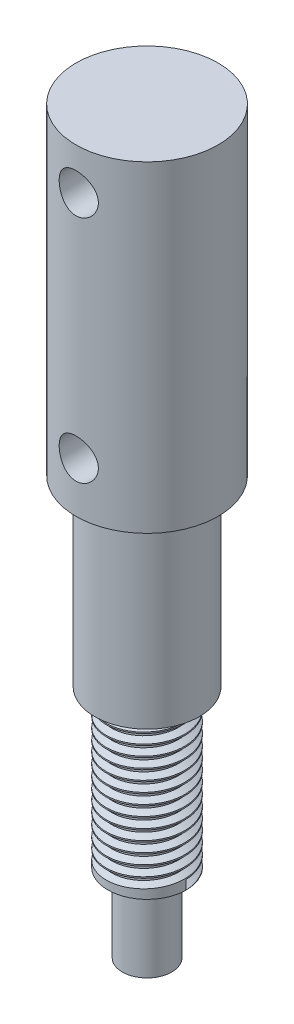
SolidWorks part; units mm, degrees
material "AISI 316 Annealed Stainless Steel Bar (SS)"
ref_plane "Front Plane" through (0, 0, 0) normal (0, 0, 1) x (1, 0, 0)
ref_plane "Top Plane" through (0, 0, 0) normal (0, 1, 0) x (1, 0, 0)
ref_plane "Right Plane" through (0, 0, 0) normal (1, 0, 0) x (0, 0, -1)
sketch "Sketch2" plane through (0, 0, 0) normal (0, 0, 1) x (1, 0, 0)
  line L0 (0, 0) -> (0, 508.8276) construction
  line L1 (0, 0) -> (6, 0)
  line L2 (0, 0) -> (0, 19.05)
  line L3 (0, 19.05) -> (6, 19.05)
  line L4 (6, 0) -> (6, 19.05)
  line L5 (0, 19.05) -> (9.525, 19.05)
  line L6 (0, 19.05) -> (0, 57.15)
  line L7 (0, 57.15) -> (9.525, 57.15)
  line L8 (9.525, 19.05) -> (9.525, 57.15)
  line L9 (0, 57.15) -> (12.721, 57.15)
  line L10 (0, 57.15) -> (0, 101.6)
  line L11 (0, 101.6) -> (12.721, 101.6)
  line L12 (12.721, 57.15) -> (12.721, 101.6)
  line L13 (0, 101.6) -> (17.272, 101.6)
  line L14 (0, 101.6) -> (0, 179.832)
  line L15 (0, 179.832) -> (17.272, 179.832)
  line L16 (17.272, 101.6) -> (17.272, 179.832)
  dimension "D1" = 78.232
  dimension "D2" = 17.272
  dimension "D4" = 44.45
  dimension "D3" = 12.721
  dimension "D5" = 38.1
  dimension "D6" = 9.525
  dimension "D7" = 19.05
  dimension "D8" = 6
revolve "Revolve1" add sketch "Sketch2" angle 360 about L0 region at (3, 9.525, 0) region at (4.7625, 38.1, 0) region at (6.3605, 79.375, 0) region at (8.636, 140.716, 0)
thread "Thread2" pitch 2.54 method cut profile "Thread Profile3" start angle 0, offset 0, length 0, pitch 2.54, diameter 19.05
ref_plane "Plane3" through (9.525, 19.05, 0) normal (0, 0, 1) x (1, 0, 0)
sketch "Thread Profile3" plane through (9.525, 19.05, 0) normal (0, 0, 1) x (1, 0, 0)
  line L0 (0, 0) -> (0, 2.54) construction
  line L11 (0, 0) -> (0, 2.2225)
  line L12 (0, 2.2225) -> (-1.3748, 1.4287)
  line L13 (-1.3748, 1.4287) -> (-1.3748, 0.7937)
  line L15 (-1.3748, 0.7937) -> (0, 0)
  line L17 (-1.3748, 1.1112) -> (0, 1.1112) construction
  point P2 (0, 0)
  dimension "Pitch" = 2.54
  dimension "Profile_Angle" = 60
  dimension "Profile_Land" = 0.635
  dimension "Profile_Height" = 1.3748
sketch "Sketch3" plane through (0, 0, 0) normal (0, 0, 1) x (1, 0, 0)
  line L0 (0, 0) -> (0, 197.3408) construction
  line L1 (17.272, 179.832) -> (-17.272, 179.832) construction
  circle A0 centre (0, 169.672) radius 4.7625
  circle A1 centre (0, 113.792) radius 4.7625
  dimension "D1" = 9.525
  dimension "D2" = 10.16
  dimension "D3" = 66.04
extrude "Cut-Extrude1" cut sketch "Sketch3" against normal through all both and the other way through all
equation "\"hole diamiter\"= 1.36in"
equation "\"wheel depth\"= 2.88"
equation "\"press_tolerance\"= 0.00165"
equation "\"wheel_connection\"= \"hole diamiter\"'https://at-machining.com/tolerance-press-fit/"
equation "\"D1@Sketch2\"=\"wheel depth\"+0.2"
equation "\"D2@Sketch2\"=\"wheel_connection\"/2"
equation "\"fitting depth\"=1.75"
equation "\"D4@Sketch2\"=\"fitting depth\""
equation "\"bearing_id\"= 1"
equation "\"bearing_connection\"= \"bearing_id\" + \"press_tolerance\"'https://at-machining.com/tolerance-press-fit/"
equation "\"D3@Sketch2\"=\"bearing_connection\"/2"
equation "\"thread length\"= 1.5"
equation "\"major_diamiter\"= 0.75 'https://www.machiningdoctor.com/threadinfo/?tid=81"
equation "\"D5@Sketch2\"=\"thread length\""
equation "\"D6@Sketch2\"=\"major_diamiter\"/2"
equation "\"coupling diamiter\"= 12mm"
equation "\"coupling lenght\"= 1.5 / 2"
equation "\"D7@Sketch2\"=\"coupling lenght\""
equation "\"D8@Sketch2\"=\"coupling diamiter\"/2"
